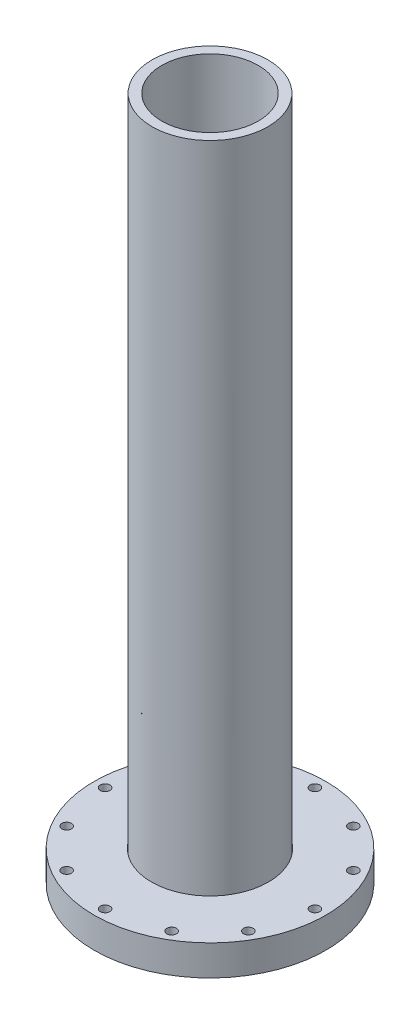
SolidWorks part; units mm, degrees
material "AISI 316 Stainless Steel Sheet (SS)"
ref_plane "Front Plane" through (0, 0, 0) normal (0, 0, 1) x (1, 0, 0)
ref_plane "Top Plane" through (0, 0, 0) normal (0, 1, 0) x (1, 0, 0)
ref_plane "Right Plane" through (0, 0, 0) normal (1, 0, 0) x (0, 0, -1)
sketch "Sketch1" plane through (0, 0, 0) normal (0, 1, 0) x (1, 0, 0)
  circle A0 centre (0, 0) radius 31.75
  circle A1 centre (0, 0) radius 38.1
  dimension "D1" = 63.5
  dimension "D2" = 76.2
extrude "Boss-Extrude1" add sketch "Sketch1" along normal blind 450
sketch "Sketch2" plane through (0, 0, 0) normal (0, 1, 0) x (1, 0, 0)
  circle A0 centre (0, 0) radius 76.2
  circle A3 centre (0, 0) radius 76.2 construction
  circle A4 centre (0, 0) radius 38.4556
  circle A5 centre (0, 0) radius 38.1 construction
  dimension "D1" = 0.3556
extrude "Boss-Extrude2" add sketch "Sketch2" along normal blind 20 separate body
hole_wizard "1/4 (0.25) Diameter Hole1" positions "Sketch4" profile "Sketch5" hole size "1/4" standard "ANSI Inch" end condition through all
sketch "Sketch4" plane through (0, 0, 0) normal (0, -1, 0) x (-1, 0, 0)
  point P0 (-69, 0)
  dimension "D1" = 69
sketch "Sketch5" plane through (69, 0, 0) normal (1, 0, 0) x (0, 0, -1)
  line L0 (0, 0) -> (0, 450)
  line L1 (0, 450) -> (3.175, 450)
  line L2 (3.175, 450) -> (3.175, 0)
  line L5 (3.175, 0) -> (0, 0)
  line L11 (0, -6.35) -> (0, 107.95) construction
  dimension "Thru Hole Dia." = 6.35
  dimension "Thru Hole Depth" = 450
ref_axis "Axis1" through (0, 472.5, 0) along (0, -1, 0)
pattern_circular "CirPattern1" count 12 over 360 about axis through (0, 472.5, 0) along (0, -1, 0) of "1/4 (0.25) Diameter Hole1"
sketch "Sketch6" plane through (0, 0, 0) normal (0, -1, 0) x (1, 0, 0)
  circle A0 centre (0, 0) radius 55.14 construction
  circle A1 centre (0, 0) radius 55.14
extrude "Cut-Extrude1" cut sketch "Sketch6" against normal blind 2
